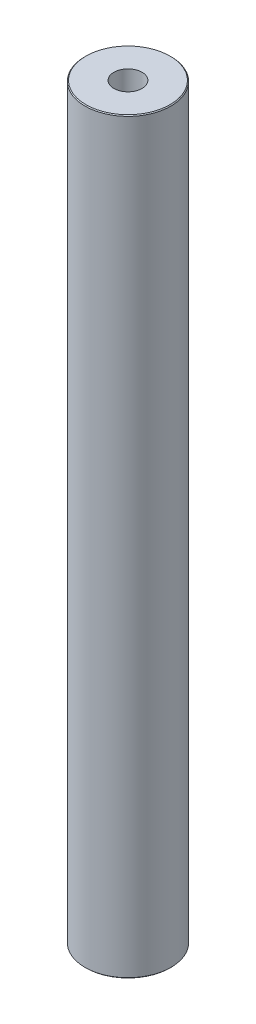
SolidWorks part; units mm, degrees
ref_plane "Front Plane" through (0, 0, 0) normal (0, 0, 1) x (1, 0, 0)
ref_plane "Top Plane" through (0, 0, 0) normal (0, 1, 0) x (1, 0, 0)
ref_plane "Right Plane" through (0, 0, 0) normal (1, 0, 0) x (0, 0, -1)
sketch "Sketch1" plane through (0, 0, 0) normal (0, 1, 0) x (1, 0, 0)
  circle A0 centre (0, 0) radius 15
  dimension "SHAFT_OD" = 30
extrude "Boss-Extrude1" add sketch "Sketch1" along normal blind 261.2443
sketch "Sketch2" plane through (0, 0, 0) normal (0, 1, 0) x (1, 0, 0)
  circle A0 centre (0, 0) radius 4.924
  dimension "BORE_D" = 9.8479
extrude "Cut-Extrude1" cut sketch "Sketch2" along normal through all
chamfer "Chamfer1" distance 0.2971 angle 45 2 edges at (0, 261.2443, 15) (0, 0, 15)
